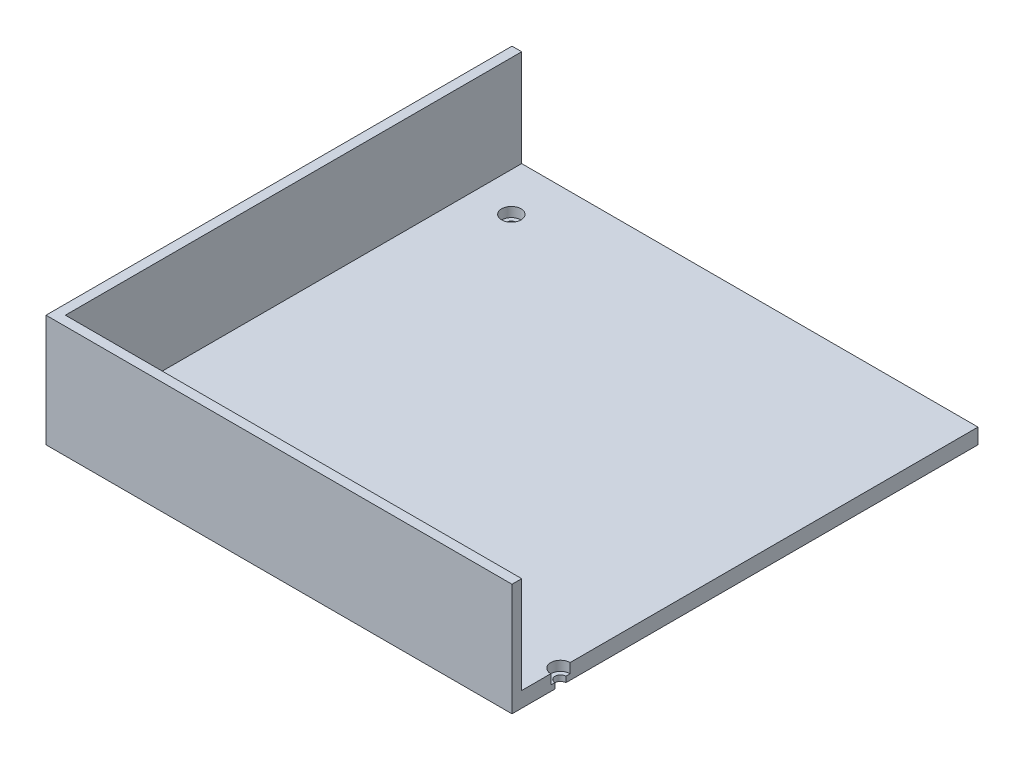
SolidWorks part; units mm, degrees
ref_plane "Front Plane" through (0, 0, 0) normal (0, 0, 1) x (1, 0, 0)
ref_plane "Top Plane" through (0, 0, 0) normal (0, 1, 0) x (1, 0, 0)
ref_plane "Right Plane" through (0, 0, 0) normal (1, 0, 0) x (0, 0, -1)
sketch "Sketch1" plane through (0, 0, 0) normal (0, 1, 0) x (1, 0, 0)
  line L1 (-96.2, 96.2) -> (96.2, 96.2)
  line L2 (-96.2, 96.2) -> (-96.2, -96.2)
  line L3 (-96.2, -96.2) -> (96.2, -96.2)
  line L4 (96.2, 96.2) -> (96.2, -96.2)
  line L5 (-96.2, 96.2) -> (96.2, -96.2) construction
  line L6 (-96.2, -96.2) -> (96.2, 96.2) construction
  point P0 (0, 0)
  dimension "D1" = 192.4
  dimension "D2" = 192.4
extrude "Boss-Extrude1" add sketch "Sketch1" along normal blind 6.35
sketch "Sketch2" plane through (0, 6.35, 0) normal (0, 1, 0) x (1, 0, 0)
  line L2 (-92.2, 92.2) -> (-92.2, -92.2)
  line L3 (-92.2, -92.2) -> (92.2, -92.2)
  line L4 (96.2, -96.2) -> (96.2, 96.2)
  line L5 (96.2, 96.2) -> (-96.2, 96.2)
  line L6 (-96.2, 96.2) -> (-96.2, -96.2)
  line L7 (-96.2, -96.2) -> (96.2, -96.2)
  line L10 (-96.2, 96.2) -> (-96.2, -96.2)
  line L11 (-96.2, -96.2) -> (96.2, -96.2)
  line L12 (92.2, 92.2) -> (-92.2, 92.2) construction
  line L13 (96.2, 96.2) -> (-96.2, 96.2) construction
  line L14 (92.2, -92.2) -> (92.2, 92.2) construction
  line L15 (96.2, -96.2) -> (96.2, 96.2) construction
  line L16 (-92.2, 92.2) -> (-92.2, 96.2)
  line L17 (96.2, 96.2) -> (-96.2, 96.2) construction
  line L18 (-92.2, 96.2) -> (-96.2, 96.2)
  line L19 (92.2, -92.2) -> (96.2, -92.2)
  line L20 (96.2, -96.2) -> (96.2, 96.2) construction
  line L21 (96.2, -92.2) -> (96.2, -96.2)
  dimension "D1" = 0
  dimension "D2" = 4
extrude "Boss-Extrude2" add sketch "Sketch2" along normal blind 40
sketch "Sketch3" plane through (0, 6.35, 0) normal (0, 1, 0) x (1, 0, 0)
  line L0 (-96.2, -96.2) -> (96.2, -96.2) construction
  line L1 (-96.2, 96.2) -> (-56.2, 96.2) construction
  line L2 (-96.2, 96.2) -> (-96.2, -96.2) construction
  line L3 (-96.2, -96.2) -> (-56.2, -96.2) construction
  line L4 (-56.2, 96.2) -> (-56.2, -96.2) construction
  line L5 (96.2, -92.2) -> (96.2, 96.2) construction
  line L6 (-96.2, 96.2) -> (96.2, 96.2) construction
  line L7 (-96.2, 96.2) -> (-96.2, 55.6473) construction
  line L8 (-96.2, 55.6473) -> (96.2, 55.6473) construction
  line L9 (96.2, 96.2) -> (96.2, 55.6473) construction
  line L10 (96.2, -76.2) -> (-96.2, -76.2) construction
  line L11 (-96.2, -96.2) -> (96.2, -96.2) construction
  line L12 (-96.2, -96.2) -> (-96.2, -56.2) construction
  line L13 (-96.2, -56.2) -> (96.2, -56.2) construction
  line L14 (96.2, -96.2) -> (96.2, -56.2) construction
  line L15 (-76.2, -96.2) -> (-76.2, 96.2) construction
  line L16 (96.2, 75.9237) -> (-96.2, 75.9237) construction
  circle A0 centre (-76.2, -76.2) radius 2.25
  circle A1 centre (-76.2, 75.9237) radius 2.25
  circle A2 centre (96.2, -76.2) radius 2.25
  point P15 (96.2, -76.2)
  point P21 (-76.2, -76.2)
  point P23 (-76.2, 75.9237)
  point P33 (96.2, -76.2)
  dimension "D4" = 4.5
  dimension "D1" = 40
  dimension "D2" = 40.5527
  dimension "D3" = 40
hole_wizard "CBORE for M4 SHCS1" positions "Sketch3" profile "Sketch4" counterbore size "M4" standard "ANSI Metric" end condition up to next
sketch "Sketch4" plane through (96.2, 6.35, 76.2) normal (1, 0, 0) x (0, 0, 1)
  line L0 (0, 0) -> (0, 6.35)
  line L1 (0, 6.35) -> (2.25, 6.35)
  line L3 (2.25, 6.35) -> (2.25, 4)
  line L4 (2.25, 4) -> (4, 4)
  line L5 (4, 4) -> (4, 0)
  line L7 (4, 0) -> (0, 0)
  line L11 (0, -6.35) -> (0, 107.95) construction
  dimension "Thru Hole Dia." = 4.5
  dimension "Thru Hole Depth" = 6.35
  dimension "C'Bore Dia." = 8
  dimension "C'Bore Depth" = 4
equation "\"D2@Sketch1\"=384.8/2"
